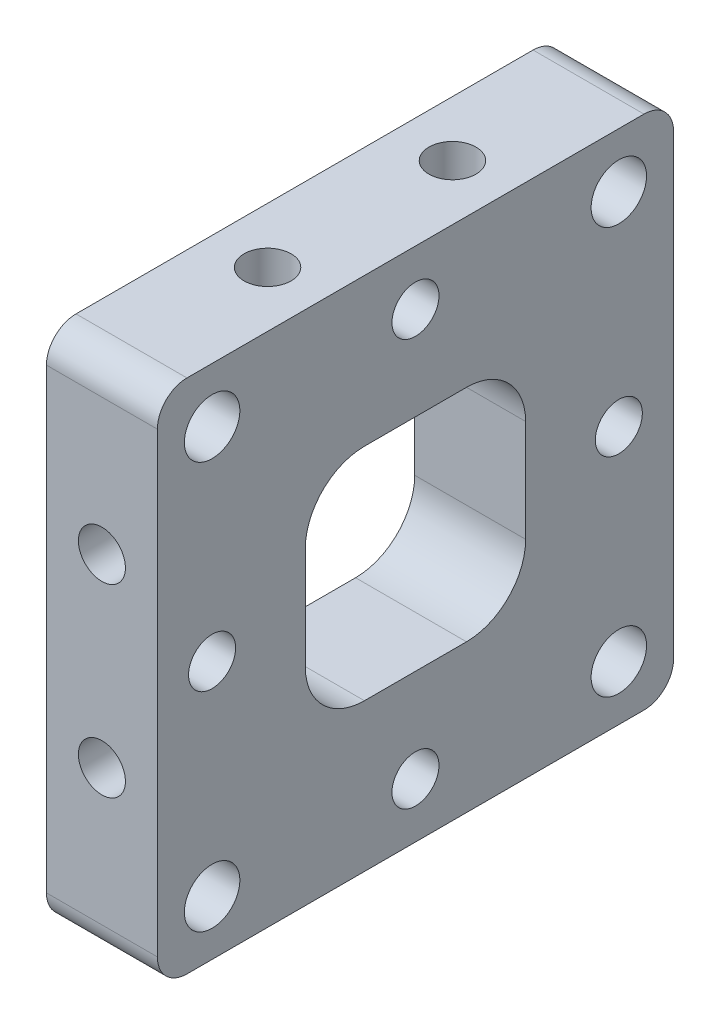
SolidWorks part; units mm, degrees
material "6061-T6 (SS)"
ref_plane "Front Plane" through (0, 0, 0) normal (0, 0, 1) x (1, 0, 0)
ref_plane "Top Plane" through (0, 0, 0) normal (0, 1, 0) x (1, 0, 0)
ref_plane "Right Plane" through (0, 0, 0) normal (1, 0, 0) x (0, 0, -1)
sketch "Sketch1" plane through (0, 0, 0) normal (1, 0, 0) x (0, 0, -1)
  line L0 (17.4625, 17.4625) -> (-17.4625, 17.4625) construction
  line L1 (-22.1615, -22.1615) -> (22.1615, -22.1615) construction
  line L2 (-22.1615, -22.1615) -> (-22.1615, 22.1615) construction
  line L3 (-22.1615, 22.1615) -> (22.1615, 22.1615) construction
  line L4 (22.1615, -22.1615) -> (22.1615, 22.1615) construction
  line L5 (-22.1615, -22.1615) -> (22.1615, 22.1615) construction
  line L6 (-22.1615, 22.1615) -> (22.1615, -22.1615) construction
  line L7 (22.1615, 22.1615) -> (-22.1615, 22.1615)
  line L8 (-22.1615, 22.1615) -> (-22.1615, -22.1615)
  line L9 (-22.1615, -22.1615) -> (22.1615, -22.1615)
  line L10 (22.1615, -22.1615) -> (22.1615, 22.1615)
  line L11 (-17.4625, 17.4625) -> (-17.4625, -17.4625) construction
  line L12 (17.4625, -17.4625) -> (-17.4625, -17.4625) construction
  line L13 (17.4625, 17.4625) -> (17.4625, -17.4625) construction
  line L14 (-28.3465, -23.114) -> (27.3656, -23.114) construction
  line L15 (-25.4, 25.4) -> (25.4, 25.4) construction
  line L16 (-25.4, 25.4) -> (-25.4, -25.4) construction
  line L17 (-25.4, -25.4) -> (25.4, -25.4) construction
  line L18 (25.4, 25.4) -> (25.4, -25.4) construction
  line L19 (-25.4, 25.4) -> (25.4, -25.4) construction
  line L20 (-25.4, -25.4) -> (25.4, 25.4) construction
  line L21 (22.1615, -22.1615) -> (-22.1615, -22.1615) construction
  line L22 (22.1615, 22.1615) -> (22.1615, -22.1615) construction
  line L23 (-22.1615, 22.1615) -> (-22.1615, -22.1615) construction
  circle A0 centre (-17.4625, 17.4625) radius 2.3813
  circle A1 centre (17.4625, 17.4625) radius 2.3813
  circle A2 centre (-17.4625, -17.4625) radius 2.3813
  circle A3 centre (17.4625, -17.4625) radius 2.3813
  point P4 (0, 0)
  point P16 (0, 0)
  dimension "D4" = 4.7625
  dimension "D1" = 3.2385
  dimension "D2" = 34.925
  dimension "D5" = 50.8
  dimension "D3" = 2.286
extrude "Boss-Extrude1" add sketch "Sketch1" along normal mid plane 9.525
fillet "Fillet1" radius 2.54 4 edges at (0, -22.1615, -22.1615) (0, -22.1615, 22.1615) (0, 22.1615, 22.1615) (0, 22.1615, -22.1615)
hole_wizard "#10-32 Tapped Hole1" positions "Sketch11" profile "Sketch12" tap size "#10-32" standard "ANSI Inch"
sketch "Sketch11" plane through (-4.7625, 0, 0) normal (-1, 0, 0) x (0, 0, 1)
  line L7 (0, 17.4625) -> (0, -17.4625) construction
  line L9 (-17.4625, 0) -> (17.4625, 0) construction
  line L11 (17.4625, 17.4625) -> (-17.4625, 17.4625) construction
  point P77 (0, 0)
  point P78 (0, 0)
  point P81 (0, 17.4625)
  point P84 (-17.4625, 0)
  point P87 (17.4625, 0)
  point P90 (0, -17.4625)
sketch "Sketch12" plane through (-4.7625, -17.4625, 0) normal (0, 1, 0) x (0, 0, 1)
  line L0 (0, 0) -> (0, 13.2529)
  line L1 (0, 13.2529) -> (2.0193, 12.0396)
  line L2 (2.0193, 12.0396) -> (2.0193, 0)
  line L5 (2.0193, 0) -> (0, 0)
  line L10 (0, 13.2529) -> (-2.0193, 12.0396) construction
  line L11 (0, -6.35) -> (0, 107.95) construction
  dimension "Tap Drill Dia." = 4.0386
  dimension "Tap Drill Depth" = 12.0396
  dimension "Drill Angle" = 118
cosmetic thread "Hole Thread6" parameters "D1"=9.525, "D2"=4.826
cosmetic thread "Hole Thread7" parameters "D1"=9.525, "D2"=4.826
cosmetic thread "Hole Thread8" parameters "D1"=9.525, "D2"=4.826
cosmetic thread "Hole Thread9" parameters "D1"=9.525, "D2"=4.826
hole_wizard "#10-32 Tapped Hole2" positions "Sketch13" profile "Sketch15" tap size "#10-32" standard "ANSI Inch"
sketch "Sketch13" plane through (0, 22.1615, 0) normal (0, 1, 0) x (1, 0, 0)
  line L0 (0, 7.9375) -> (0, -7.9375) construction
  point P1 (0, 7.9375)
  point P2 (0, -7.9375)
  point P14 (0, 0)
  dimension "D1" = 15.875
sketch "Sketch15" plane through (0, 22.1615, -7.9375) normal (1, 0, 0) x (0, 0, 1)
  line L0 (0, 0) -> (0, 10.7383)
  line L1 (0, 10.7383) -> (2.0193, 9.525)
  line L2 (2.0193, 9.525) -> (2.0193, 0)
  line L5 (2.0193, 0) -> (0, 0)
  line L10 (0, 10.7383) -> (-2.0193, 9.525) construction
  line L11 (0, -6.35) -> (0, 107.95) construction
  dimension "Tap Drill Dia." = 4.0386
  dimension "Tap Drill Depth" = 9.525
  dimension "Drill Angle" = 118
cosmetic thread "Hole Thread10" parameters "D1"=9.525, "D2"=4.826
cosmetic thread "Hole Thread11" parameters "D1"=9.525, "D2"=4.826
ref_axis "Axis1" through (0, 0, 0) along (1, 0, 0)
pattern_circular "CirPattern1" count 4 every 90 about axis through (0, 0, 0) along (1, 0, 0) skipping 2 of "#10-32 Tapped Hole2"
hole_wizard "#10-32 Tapped Hole3" positions "Sketch16" profile "Sketch18" tap size "#10-32" standard "ANSI Inch"
sketch "Sketch16" plane through (0, -22.1615, 0) normal (0, -1, 0) x (-1, 0, 0)
  line L0 (0, 11.1125) -> (0, -11.1125) construction
  point P0 (0, -11.1125)
  point P2 (0, 11.1125)
  point P8 (0, 0)
  dimension "D1" = 22.225
sketch "Sketch18" plane through (0, -22.1615, 11.1125) normal (1, 0, 0) x (0, 0, -1)
  line L0 (0, 0) -> (0, 10.7383)
  line L1 (0, 10.7383) -> (2.0193, 9.525)
  line L2 (2.0193, 9.525) -> (2.0193, 0)
  line L5 (2.0193, 0) -> (0, 0)
  line L10 (0, 10.7383) -> (-2.0193, 9.525) construction
  line L11 (0, -6.35) -> (0, 107.95) construction
  dimension "Tap Drill Dia." = 4.0386
  dimension "Tap Drill Depth" = 9.525
  dimension "Drill Angle" = 118
cosmetic thread "Hole Thread12" parameters "D1"=8.89, "D2"=4.826
cosmetic thread "Hole Thread13" parameters "D1"=8.89, "D2"=4.826
sketch "Sketch19" plane through (4.7625, 0, 0) normal (1, 0, 0) x (0, 0, -1)
  line L0 (9.4615, -9.4615) -> (-9.4615, 9.4615) construction
  line L1 (-9.4615, 9.4615) -> (9.4615, 9.4615)
  line L2 (-9.4615, 9.4615) -> (-9.4615, -9.4615)
  line L3 (-9.4615, -9.4615) -> (9.4615, -9.4615)
  line L4 (9.4615, 9.4615) -> (9.4615, -9.4615)
  line L5 (19.6215, 22.1615) -> (-19.6215, 22.1615) construction
  dimension "D1" = 12.7
extrude "Cut-Extrude1" cut sketch "Sketch19" against normal through all
fillet "Fillet2" radius 5.08 4 edges at (0, 9.4615, -9.4615) (0, -9.4615, -9.4615) (0, -9.4615, 9.4615) (0, 9.4615, 9.4615)
